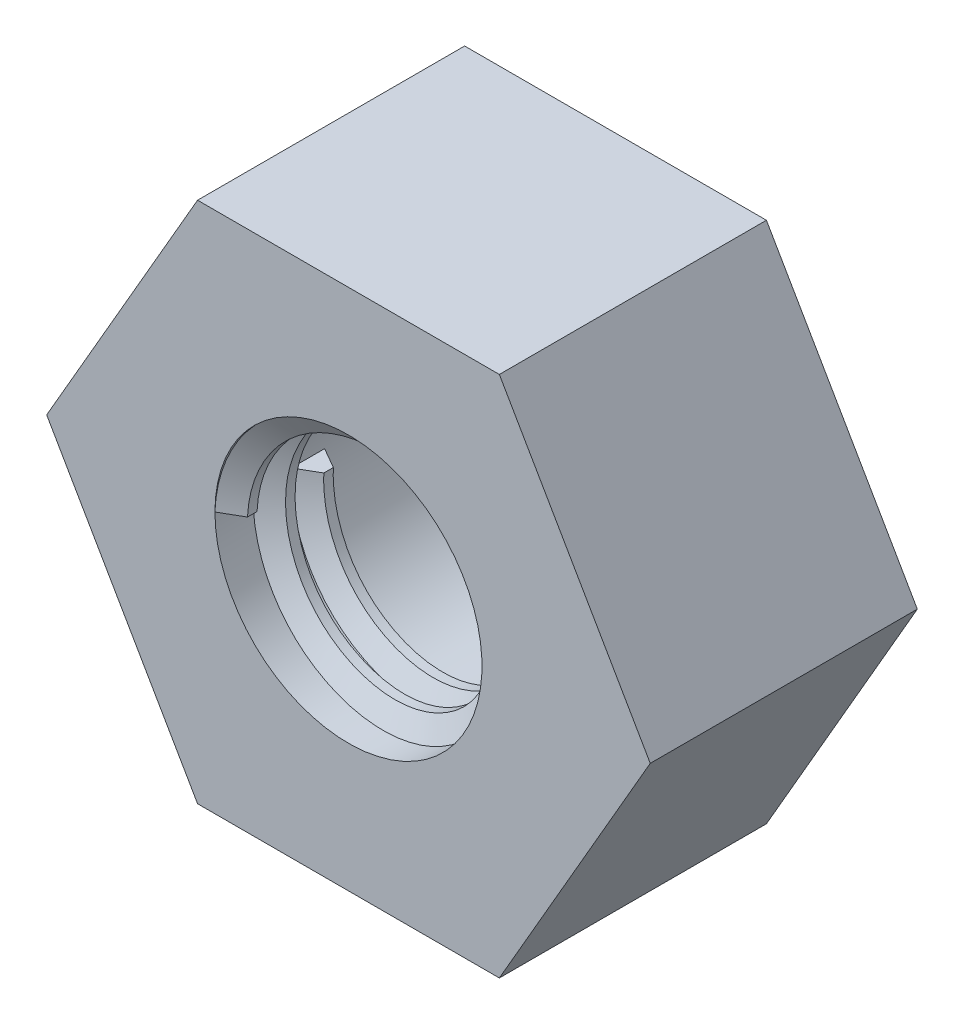
SolidWorks part; units mm, degrees
material "1023 Carbon Steel Sheet (SS)"
ref_plane "Front Plane" through (0, 0, 0) normal (0, 0, 1) x (1, 0, 0)
ref_plane "Top Plane" through (0, 0, 0) normal (0, 1, 0) x (1, 0, 0)
ref_plane "Right Plane" through (0, 0, 0) normal (1, 0, 0) x (0, 0, -1)
sketch "Sketch1" plane through (0, 0, 0) normal (0, 0, 1) x (1, 0, 0)
  line L1 (3.9548, 0) -> (1.9774, 3.425)
  line L2 (1.9774, 3.425) -> (-1.9774, 3.425)
  line L3 (-1.9774, 3.425) -> (-3.9548, 0)
  line L4 (-3.9548, 0) -> (-1.9774, -3.425)
  line L5 (-1.9774, -3.425) -> (1.9774, -3.425)
  line L6 (1.9774, -3.425) -> (3.9548, 0)
  circle A0 centre (0, 0) radius 3.425 construction
  circle A1 centre (0, 0) radius 1.75
  dimension "D2" = 3.5
  dimension "D1" = 6.85
  dimension "D3" = 3.425
extrude "Boss-Extrude1" add sketch "Sketch1" along normal blind 3.5
thread "Thread1" pitch 0.5 method extrude profile "Thread Profile1" start angle 0, offset 0, length 1, pitch 0.5, diameter 3.5
ref_plane "Plane1" through (-1.75, 0, 3.5) normal (0, -1, 0) x (-1, 0, 0)
sketch "Thread Profile1" plane through (-1.75, 0, 3.5) normal (0, -1, 0) x (-1, 0, 0)
  line L0 (0, 0) -> (0, 0.5) construction
  line L11 (0, 0) -> (0, 0.4375)
  line L12 (0, 0.4375) -> (-0.2706, 0.2812)
  line L13 (-0.2706, 0.2812) -> (-0.2706, 0.1562)
  line L15 (-0.2706, 0.1562) -> (0, 0)
  line L17 (-0.2706, 0.2187) -> (0, 0.2187) construction
  point P2 (0, 0)
  dimension "Pitch" = 0.5
  dimension "Profile_Angle" = 60
  dimension "Profile_Land" = 0.125
  dimension "Profile_Height" = 0.2706
